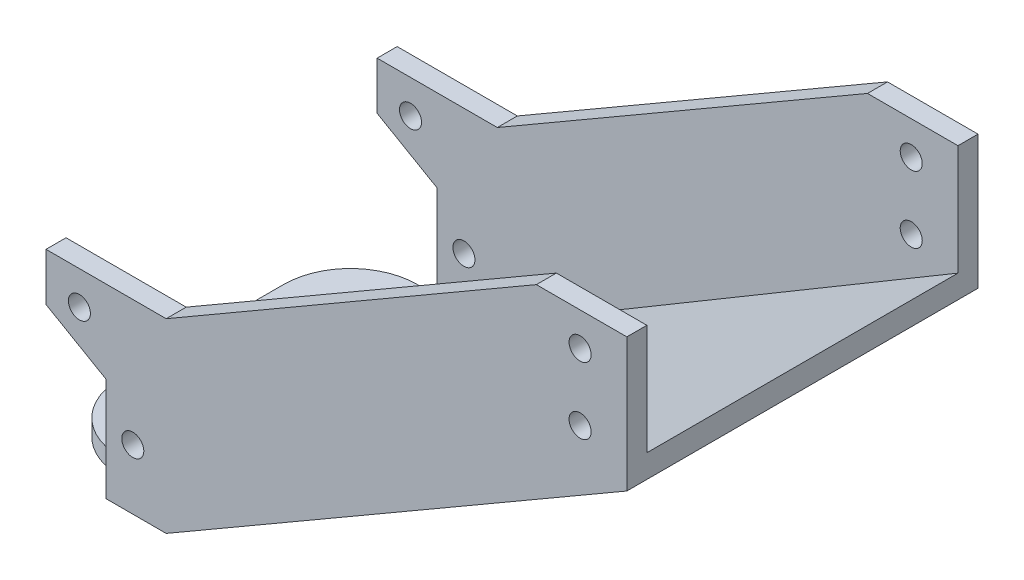
SolidWorks part; units mm, degrees
material "ABS"
ref_plane "Front Plane" through (0, 0, 0) normal (0, 0, 1) x (1, 0, 0)
ref_plane "Top Plane" through (0, 0, 0) normal (0, 1, 0) x (1, 0, 0)
ref_plane "Right Plane" through (0, 0, 0) normal (1, 0, 0) x (0, 0, -1)
sketch "Sketch1" plane through (0, 0, 0) normal (0, 0, 1) x (1, 0, 0)
  line L1 (-13, 18.8564) -> (-13, 11.6962)
  line L2 (-13, 11.6962) -> (-4, 6.5)
  line L3 (-4, 6.5) -> (-4, -9)
  line L4 (-4, -9) -> (5, -9)
  line L5 (5, -9) -> (5, 18.8564)
  line L7 (-8, 13.8564) -> (0, 0) construction
  line L8 (-13, 18.8564) -> (5, 18.8564)
  line L9 (75, 51) -> (75, 31) construction
  line L10 (5, -9) -> (74, 31)
  line L11 (74, 31) -> (74, 51)
  line L12 (74, 51) -> (60.4477, 51)
  line L13 (60.4477, 51) -> (5, 18.8564)
  line L14 (-4, -6.5) -> (5, -6.5)
  line L15 (5, -6.5) -> (74, 34.4676)
  circle A0 centre (0, 0) radius 1.65
  circle A1 centre (-8, 13.8564) radius 1.65
  circle A2 centre (67, 46) radius 1.65
  circle A3 centre (67, 36) radius 1.65
  point P20 (74, 41)
  dimension "D2" = 3.3
  dimension "D15" = 3.3
  dimension "D1" = 16
  dimension "D3" = 60
  dimension "D4" = 5
  dimension "D5" = 9
  dimension "D6" = 5
  dimension "D7" = 4
  dimension "D8" = 6.5
  dimension "D9" = 5
  dimension "D10" = 120
  dimension "D11" = 20
  dimension "D12" = 70
  dimension "D13" = 60
  dimension "D14" = 1
  dimension "D16" = 5
  dimension "D17" = 10
  dimension "D18" = 7
  dimension "D19" = 2.5
  dimension "D20" = 3
extrude "Boss-Extrude1" add sketch "Sketch1" along normal blind 3 contours L8 L1 L2 L3 L4 L5 A1 A0 | L12 L13 L5 L10 L11 | L15 L5 L10 L11 | L14 L3 L4 L5 region at (-1.7694, 8.3928, 0) region at (38.0111, 25.252, 0) region at (41.3647, 13.586, 0) region at (0.5, -7.75, 0)
extrude "Boss-Extrude2" add sketch "Sketch1<3>" against normal blind 46.6 contours L14 L3 L4 L5 | L15 L5 L10 L11 region at (41.3647, 13.586, 0) region at (0.5, -7.75, 0)
sketch "Sketch1<3>" plane through (0, 0, 0) normal (0, 0, 1) x (1, 0, 0) same geometry as "Sketch1"
extrude "Boss-Extrude3" add sketch "Sketch1<4>" against normal blind 3 from surface contours L3 L14 L5 L8 L1 L2 A1 A0 | L14 L3 L4 L5 | L15 L5 L10 L11 | L5 L15 L11 L12 L13 A3 A2 region at (-1.7694, 8.3928, 0) region at (38.0111, 25.252, 0) region at (41.3647, 13.586, 0) region at (0.5, -7.75, 0) starting at face at (25, 5.7446, -46.6)
sketch "Sketch1<4>" plane through (0, 0, 0) normal (0, 0, 1) x (1, 0, 0) same geometry as "Sketch1"
sketch "Sketch2" plane through (0, -9, 0) normal (0, -1, 0) x (1, 0, 0)
  line L0 (1, -23.3) -> (-1, -23.3) construction
  line L1 (1, -24.95) -> (-1, -24.95)
  line L2 (1, -21.65) -> (-1, -21.65)
  line L3 (-4, 3) -> (-4, -49.6) construction
  arc A0 (1, -24.95) -> (1, -21.65) centre (1, -23.3) ccw
  arc A1 (-1, -21.65) -> (-1, -24.95) centre (-1, -23.3) ccw
  point P2 (0, -23.3)
  point P9 (-4, -23.3)
  dimension "D1" = 4
  dimension "D2" = 3.3
  dimension "D3" = 2
extrude "Cut-Extrude1" cut sketch "Sketch2" against normal blind 88.5
sketch "Sketch3" plane through (-4, 0, 0) normal (-1, 0, 0) x (0, 0, 1)
  line L0 (-46.6, -6.5) -> (0, -6.5) construction
  line L1 (-45.6, -6.5) -> (-1, -6.5)
  line L2 (-45.6, -6.5) -> (-45.6, -9)
  line L3 (-45.6, -9) -> (-1, -9)
  line L4 (-1, -6.5) -> (-1, -9)
  line L5 (3, -9) -> (-49.6, -9) construction
  dimension "D1" = 1
  dimension "D2" = 1
extrude "Boss-Extrude4" add sketch "Sketch3" along normal blind 12
fillet "Fillet1" radius 10 2 edges at (-16, -7.75, -1) (-16, -7.75, -45.6)
hole_wizard "CSK SLOT for M3 Countersunk Flat Head Screw1" positions "Sketch4" profile "Sketch5" size "M3" standard "ISO" slot yes end condition up to next
sketch "Sketch4" plane through (0, -9, 0) normal (0, -1, 0) x (-1, 0, 0)
  line L0 (2.5, 23.3) -> (-2.5, 23.3) construction
  line L1 (-5, -3) -> (-5, 49.6) construction
  point P0 (0, 23.3)
  point P10 (-5, 23.3)
  dimension "D1" = 5
sketch "Sketch5" plane through (0, -9, -23.3) normal (1, 0, 0) x (0, 0, -1)
  line L0 (0, 0) -> (0, 60)
  line L1 (0, 60) -> (1.825, 60)
  line L2 (1.8, 59.975) -> (1.8, 1.35)
  line L3 (1.8, 1.35) -> (3.15, 0)
  line L5 (3.15, 0) -> (0, 0)
  line L6 (-1.8, 1.35) -> (-3.15, 0) construction
  line L7 (1.825, 60) -> (1.8, 59.975)
  line L8 (-1.825, 60) -> (-1.8, 59.975) construction
  line L11 (0, -6.35) -> (0, 107.95) construction
  dimension "Thru Hole Dia." = 3.6
  dimension "Thru Hole Depth" = 60
  dimension "Near C'Sink Dia." = 6.3
  dimension "Near C'Sink Angle" = 90
  dimension "Far C'Sink Dia." = 3.65
  dimension "Far C'Sink Angle" = 90
equation "\"D1@Sketch3\"=\"D2@Sketch3\""
